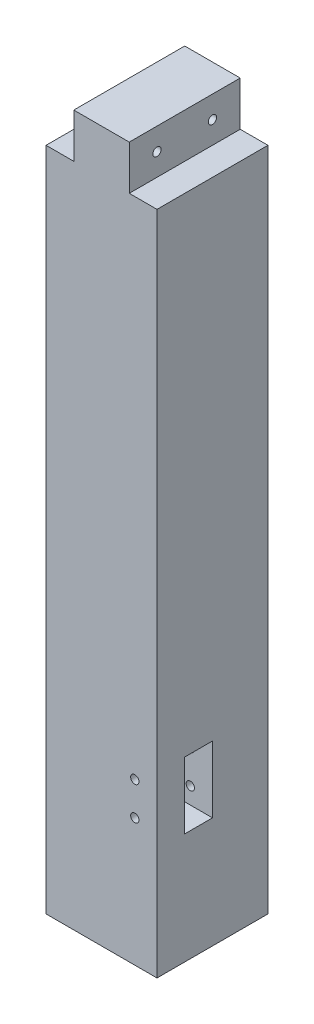
SolidWorks part; units mm, degrees
ref_plane "Front Plane" through (0, 0, 0) normal (0, 0, 1) x (1, 0, 0)
ref_plane "Top Plane" through (0, 0, 0) normal (0, 1, 0) x (1, 0, 0)
ref_plane "Right Plane" through (0, 0, 0) normal (1, 0, 0) x (0, 0, -1)
sketch "Sketch1" plane through (0, 0, 0) normal (0, 0, 1) x (1, 0, 0)
  line L0 (0, 0) -> (0, 50000) construction
  line L1 (63.5, 381) -> (-63.5, 381)
  line L2 (63.5, 381) -> (63.5, -381)
  line L3 (63.5, -381) -> (-63.5, -381)
  line L4 (-63.5, 381) -> (-63.5, -381)
  line L5 (63.5, 381) -> (-63.5, -381) construction
  line L6 (63.5, -381) -> (-63.5, 381) construction
  line L8 (-31.75, 431.8) -> (31.75, 431.8)
  line L9 (-31.75, 431.8) -> (-31.75, 330.2)
  line L10 (-31.75, 330.2) -> (31.75, 330.2)
  line L11 (31.75, 431.8) -> (31.75, 330.2)
  line L12 (-31.75, 431.8) -> (31.75, 330.2) construction
  line L13 (-31.75, 330.2) -> (31.75, 431.8) construction
  point P0 (0, 0)
  point P8 (0, 381)
  dimension "D1" = 762
  dimension "D2" = 127
  dimension "D3" = 63.5
  dimension "D4" = 101.6
extrude "Boss-Extrude1" add sketch "Sketch1" along normal blind 127 contours L1 L11 L10 L9 L4 L3 L2 | L11 L1 L9 L10 | L11 L8 L9 L1 region at (0, -12.2621, 0) region at (0, 355.6, 0) region at (0, 406.4, 0)
sketch "Sketch2" plane through (63.5, 0, 0) normal (1, 0, 0) x (0, 0, -1)
  line L0 (-127, 381) -> (-127, -381) construction
  line L1 (-63.5, -177.8) -> (-95.25, -177.8)
  line L2 (-63.5, -177.8) -> (-63.5, -254)
  line L3 (-63.5, -254) -> (-95.25, -254)
  line L4 (-95.25, -177.8) -> (-95.25, -254)
  line L5 (-63.5, -177.8) -> (-95.25, -254) construction
  line L6 (-63.5, -254) -> (-95.25, -177.8) construction
  line L7 (-127, -381) -> (0, -381) construction
  point P0 (-79.375, -215.9)
  point P5 (-79.375, -177.8)
  dimension "D1" = 76.2
  dimension "D2" = 31.75
  dimension "D3" = 31.75
  dimension "D4" = 127
extrude "Cut-Extrude1" cut sketch "Sketch2" against normal blind 50.8
sketch "Sketch3" plane through (0, 0, 127) normal (0, 0, 1) x (1, 0, 0)
  line L0 (38.1, -177.8) -> (38.1, -254) construction
  line L4 (63.5, -254) -> (63.5, -177.8)
  line L5 (12.7, -254) -> (63.5, -254)
  line L6 (12.7, -177.8) -> (12.7, -254)
  line L7 (63.5, -177.8) -> (12.7, -177.8)
  line L8 (63.5, -254) -> (63.5, -177.8)
  line L9 (12.7, -254) -> (63.5, -254)
  line L10 (12.7, -177.8) -> (12.7, -254)
  line L11 (63.5, -177.8) -> (12.7, -177.8)
  circle A0 centre (38.1, -234.95) radius 4.7625
  circle A1 centre (38.1, -196.85) radius 4.7625
  point P10 (38.1, -215.9)
  dimension "D2" = 9.525
  dimension "D3" = 19.05
  dimension "D4" = 19.05
  dimension "D1" = 0
extrude "Cut-Extrude3" cut sketch "Sketch3" against normal blind 82.55 contours A0 L0 | L0 A0 | L0 A1 | A1 L0 region at (40.1213, -196.85, 127) region at (36.0787, -196.85, 127) region at (40.1213, -234.95, 127) region at (36.0787, -234.95, 127)
sketch "Sketch4" plane through (0, 0, 0) normal (0, 0, -1) x (-1, 0, 0)
  line L0 (63.5, 381) -> (63.5, -381) construction
  line L1 (31.75, -177.8) -> (0, -177.8)
  line L2 (31.75, -177.8) -> (31.75, -254)
  line L3 (31.75, -254) -> (0, -254)
  line L4 (0, -177.8) -> (0, -254)
  line L5 (31.75, -177.8) -> (0, -254) construction
  line L6 (31.75, -254) -> (0, -177.8) construction
  line L7 (-63.5, -381) -> (63.5, -381) construction
  point P0 (15.875, -215.9)
  dimension "D1" = 31.75
  dimension "D2" = 76.2
  dimension "D3" = 31.75
  dimension "D4" = 127
extrude "Cut-Extrude4" cut sketch "Sketch4" against normal blind 63.5
sketch "Sketch5" plane through (-63.5, 0, 0) normal (-1, 0, 0) x (0, 0, 1)
  line L0 (31.75, -254) -> (31.75, -177.8) construction
  line L4 (0, -177.8) -> (0, -254)
  line L5 (0, -254) -> (63.5, -254)
  line L6 (63.5, -254) -> (63.5, -177.8)
  line L7 (63.5, -177.8) -> (0, -177.8)
  line L8 (0, -177.8) -> (0, -254)
  line L9 (0, -254) -> (63.5, -254)
  line L10 (63.5, -254) -> (63.5, -177.8)
  line L11 (63.5, -177.8) -> (0, -177.8)
  circle A0 centre (31.75, -196.85) radius 4.7625
  circle A1 centre (31.75, -234.95) radius 4.7625
  point P10 (31.75, -215.9)
  dimension "D5" = 9.525
  dimension "D2" = 31.75
  dimension "D3" = 19.05
  dimension "D4" = 19.05
  dimension "D1" = 0
extrude "Cut-Extrude5" cut sketch "Sketch5" against normal blind 76.2 contours L0 A0 | A0 L0 | L0 A1 | A1 L0 region at (-63.5, -234.95, 29.7287) region at (-63.5, -234.95, 33.7713) region at (-63.5, -196.85, 29.7287) region at (-63.5, -196.85, 33.7713)
sketch "Sketch6" plane through (31.75, 0, 0) normal (1, 0, 0) x (0, 0, -1)
  line L0 (-127, 406.4) -> (0, 406.4) construction
  line L1 (-127, 431.8) -> (-127, 381) construction
  line L2 (0, 431.8) -> (0, 381) construction
  circle A0 centre (-95.25, 406.4) radius 4.7625
  circle A1 centre (-31.75, 406.4) radius 4.7625
  point P10 (-63.5, 406.4)
  dimension "D3" = 9.525
  dimension "D1" = 31.75
  dimension "D2" = 31.75
extrude "Cut-Extrude6" cut sketch "Sketch6" against normal through all
